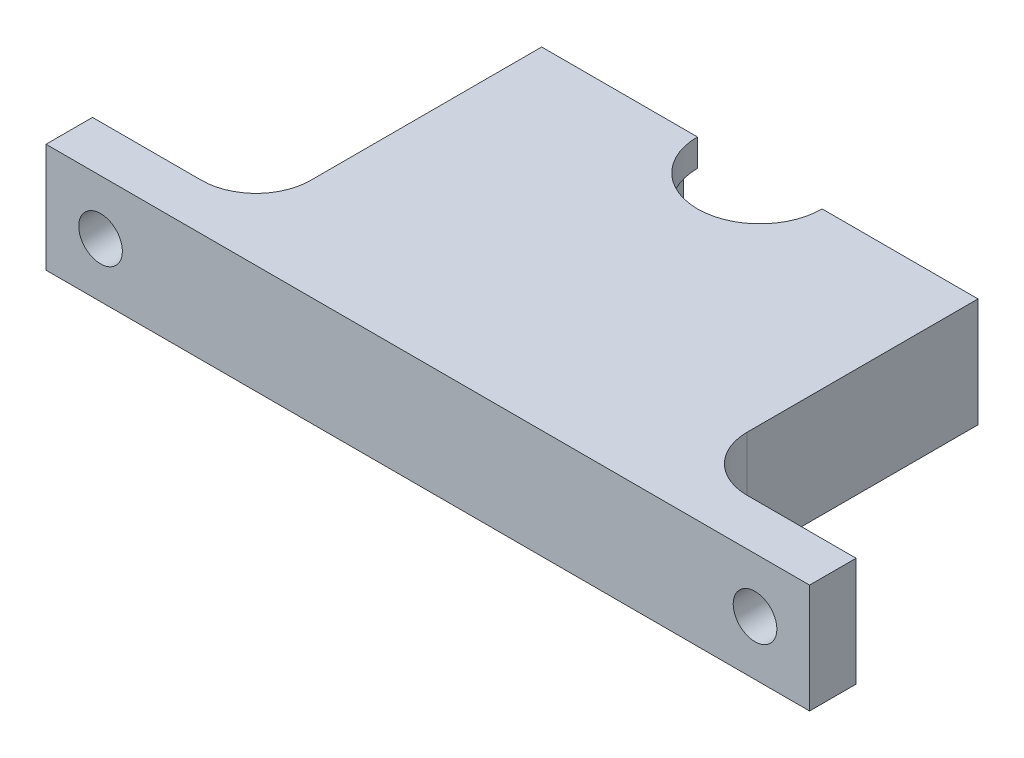
SolidWorks part; units mm, degrees
ref_plane "Front Plane" through (0, 0, 0) normal (0, 0, 1) x (1, 0, 0)
ref_plane "Top Plane" through (0, 0, 0) normal (0, 1, 0) x (1, 0, 0)
ref_plane "Right Plane" through (0, 0, 0) normal (1, 0, 0) x (0, 0, -1)
sketch "Sketch1" plane through (0, 0, 0) normal (0, 1, 0) x (1, 0, 0)
  line L0 (12.7, 0) -> (20, 0)
  line L1 (20, 0) -> (20, -30.442)
  line L2 (20, -30.442) -> (-20, -30.442)
  line L3 (-20, -30.442) -> (-20, 0)
  line L4 (-20, 0) -> (-12.7, 0)
  line L5 (-12.7, 0) -> (12.7, 0)
  circle A0 centre (0, 0) radius 5.715
  arc A1 (12.7, 0) -> (-12.7, 0) centre (0, 0) ccw
  point P8 (0, -30.442)
  dimension "D1" = 11.43
  dimension "D2" = 25.4
  dimension "D3" = 40
  dimension "D4" = 30.442
extrude "main body" add sketch "Sketch1" along normal mid plane 10 contours A0 L5 L4 L3 L2 L1 L0 region at (0, 0, 15.7838)
ref_plane "Plane1" through (0, 0, 0) normal (0, 1, 0) x (1, 0, 0)
sketch "Sketch3" plane through (0, 0, 0) normal (0, 1, 0) x (1, 0, 0)
  circle A0 centre (0, 0) radius 6.985
  dimension "D1" = 13.97
extrude "bearing cutout" cut sketch "Sketch3" against normal mid plane 5
sketch "Sketch4" plane through (0, 0, 0) normal (0, 0, -1) x (-1, 0, 0)
  line L0 (-20, 5) -> (-20, -5) construction
  line L1 (0, -5) -> (0, 5) construction
  line L2 (5.715, 5) -> (-5.715, 5) construction
  circle A0 centre (-15, 0) radius 1.5
  circle A2 centre (15, 0) radius 1.5
  point P5 (-20, 0)
  point P11 (0, 0)
  dimension "D1" = 3
  dimension "D2" = 5
extrude "top mount holes" cut sketch "Sketch4" against normal blind 10
sketch "Sketch6" plane through (0, 0, 30.442) normal (0, 0, 1) x (1, 0, 0)
  line L0 (20, 5) -> (-20, 5) construction
  line L1 (-35, 5) -> (-20, 5)
  line L2 (-35, 5) -> (-35, -5)
  line L3 (-35, -5) -> (-20, -5)
  line L4 (-20, 5) -> (-20, -5)
  line L5 (-35, 5) -> (-20, -5) construction
  line L6 (-35, -5) -> (-20, 5) construction
  line L7 (20, -5) -> (-20, -5) construction
  line L8 (-20, 5) -> (-20, -5) construction
  line L9 (0, -5) -> (0, 5) construction
  line L10 (35, -5) -> (20, -5)
  line L11 (20, 5) -> (20, -5)
  line L12 (35, 5) -> (20, 5)
  line L13 (35, 5) -> (35, -5)
  line L14 (-35, 0) -> (-20, 0) construction
  circle A0 centre (-30, 0) radius 2
  circle A1 centre (30, 0) radius 2
  point P0 (-27.5, 0)
  point P17 (0, 0)
  point P28 (-27.5, 0)
  dimension "D2" = 4
  dimension "D1" = 15
  dimension "D3" = 5
extrude "mounting holes" add sketch "Sketch6" against normal blind 4.2634
fillet "Fillet1" radius 5 2 edges at (20, 0, 26.1786) (-20, 0, 26.1786)
